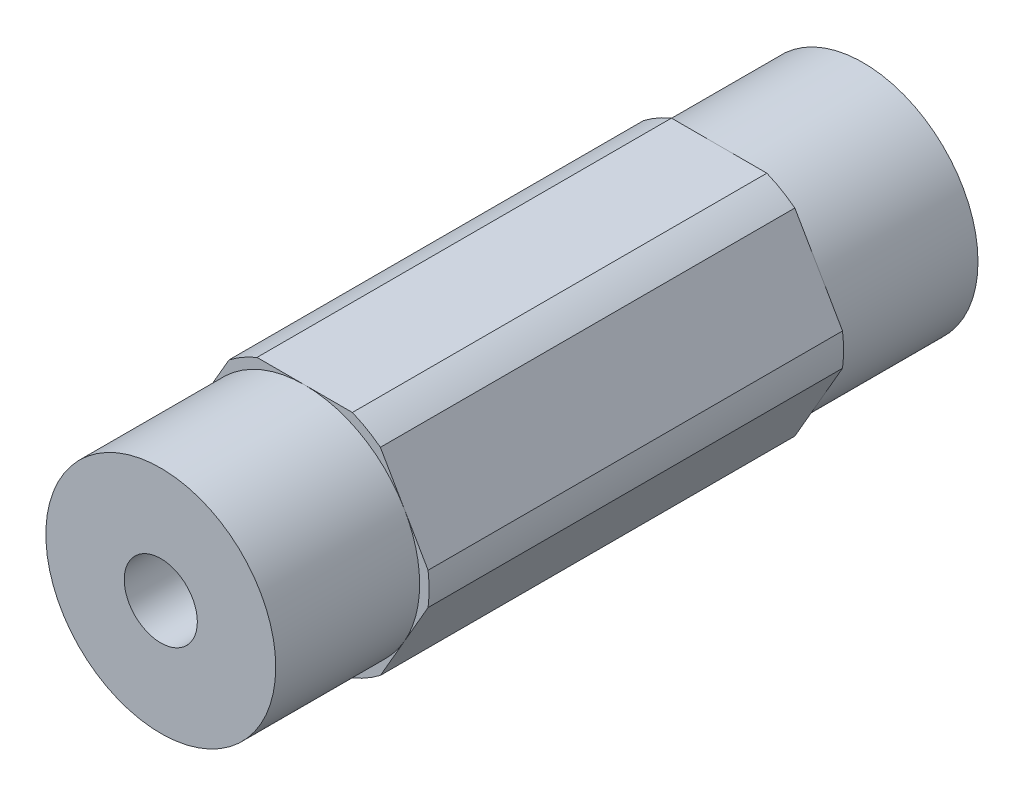
SolidWorks part; units mm, degrees
ref_plane "Front Plane" through (0, 0, 0) normal (0, 0, 1) x (1, 0, 0)
ref_plane "Top Plane" through (0, 0, 0) normal (0, 1, 0) x (1, 0, 0)
ref_plane "Right Plane" through (0, 0, 0) normal (1, 0, 0) x (0, 0, -1)
sketch "Sketch1" plane through (0, 0, 0) normal (0, 0, 1) x (1, 0, 0)
  line L1 (7.3323, 0) -> (3.6662, 6.35)
  line L2 (3.6662, 6.35) -> (-3.6662, 6.35)
  line L3 (-3.6662, 6.35) -> (-7.3323, 0)
  line L4 (-7.3323, 0) -> (-3.6662, -6.35)
  line L5 (-3.6662, -6.35) -> (3.6662, -6.35)
  line L6 (3.6662, -6.35) -> (7.3323, 0)
  circle A1 centre (0, 0) radius 6.35 construction
  dimension "D1" = 12.7
extrude "Boss-Extrude1" add sketch "Sketch1" along normal mid plane 38.7985 contours L3 L4 L5 L6 L1 L2
sketch "Sketch2" plane through (0, 0, 19.3992) normal (0, 0, 1) x (1, 0, 0)
  circle A0 centre (0, 0) radius 6.35
extrude "Cut-Extrude2" cut sketch "Sketch2" against normal blind 7.9502 flip side to cut
sketch "Sketch3" plane through (0, 0, 19.3992) normal (0, 0, 1) x (1, 0, 0)
  circle A0 centre (0, 0) radius 6.875
  dimension "D1" = 13.75
extrude "Cut-Extrude4" cut sketch "Sketch3" against normal through all flip side to cut
mirror "Mirror1" about plane through (0, 0, 0) normal (0, 0, 1) of "Cut-Extrude2"
sketch "Sketch4" plane through (0, 0, 19.3992) normal (0, 0, 1) x (1, 0, 0)
  circle A0 centre (0, 0) radius 2.0193
  dimension "D1" = 4.0386
extrude "Cut-Extrude5" cut sketch "Sketch4" against normal through all
equation "\"D1@Boss-Extrude1\"=1.5225in+0.005"
